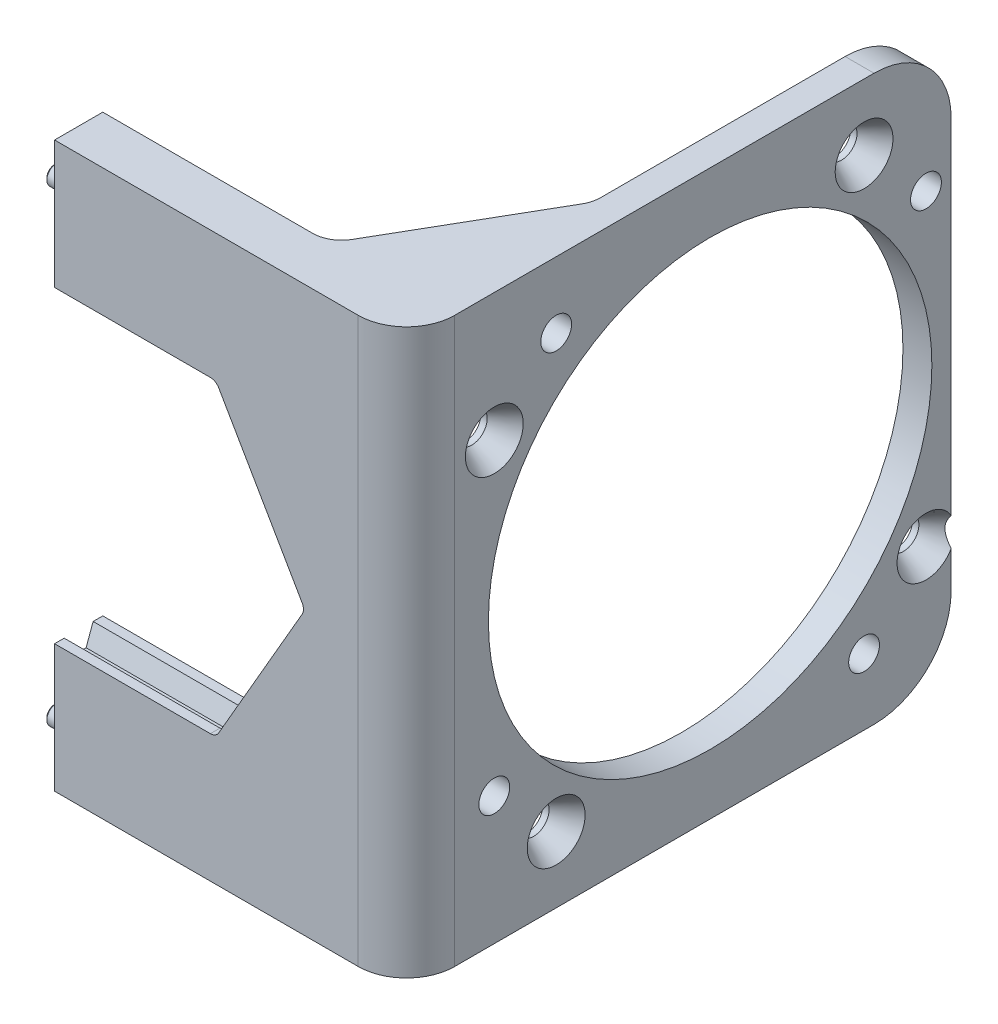
SolidWorks part; units mm, degrees
material "6061 合金"
ref_plane "前视基准面" through (0, 0, 0) normal (0, 0, 1) x (1, 0, 0)
ref_plane "上视基准面" through (0, 0, 0) normal (0, 1, 0) x (1, 0, 0)
ref_plane "右视基准面" through (0, 0, 0) normal (1, 0, 0) x (0, 0, -1)
other "Configuration Table"
sketch "草图1" plane through (0, 0, 0) normal (0, 0, 1) x (1, 0, 0)
  line L0 (-10.7623, 0) -> (8.7048, 0) construction
  line L1 (0, 6.2516) -> (0, -8.3883) construction
  circle A0 centre (0, 0) radius 18
  dimension "D1" = 36
extrude "凸台-拉伸1" add sketch "草图1" along normal blind 5
sketch "草图8" plane through (0, 0, 0) normal (0, 0, 1) x (1, 0, 0)
  line L0 (37.5243, 0) -> (-36.7763, 0) construction
  line L1 (0, 34.2207) -> (0, -32.974) construction
  line L2 (0, 26.25) -> (31, 26.25)
  line L3 (31, 26.25) -> (31, -26.25)
  line L4 (31, -26.25) -> (0, -26.25)
  line L5 (0, -26.25) -> (0, -18)
  line L6 (0, 26.25) -> (0, 18)
  circle A0 centre (0, 0) radius 18 construction
  arc A1 (0, -18) -> (0, 18) centre (0, 0) ccw
  dimension "D1" = 52.5
  dimension "D2" = 31
extrude "凸台-拉伸2" add sketch "草图8" along normal up to surface (5 mm away) up to face at (18, 0, 5)
sketch "草图9" plane through (0, 0, 0) normal (0, 0, -1) x (-1, 0, 0)
  line L0 (-31, 26.25) -> (0, 26.25) construction
  line L1 (-31, -26.25) -> (-26, -26.25)
  line L2 (-31, -26.25) -> (-31, 26.25)
  line L3 (-31, 26.25) -> (-26, 26.25)
  line L4 (-26, -26.25) -> (-26, 26.25)
  dimension "D1" = 5
extrude "凸台-拉伸3" add sketch "草图9" along normal blind 51.5
sketch "草图12" plane through (31, 0, 0) normal (1, 0, 0) x (0, 0, -1)
  line L1 (26.5, 0) -> (48.8882, 15.9693) construction
  line L2 (42.4693, 22.3882) -> (26.5, 0) construction
  line L3 (-6.3808, 0) -> (26.5, 0) construction
  line L4 (26.5, 0) -> (4.1118, 15.9693) construction
  line L5 (-5, -26.25) -> (-5, 26.25) construction
  circle A0 centre (26.5, 0) radius 27.5 construction
  circle A1 centre (4.1118, 15.9693) radius 1.6
  circle A2 centre (42.4693, 22.3882) radius 1.6
  circle A3 centre (48.8882, -15.9693) radius 1.6
  circle A4 centre (10.5307, -22.3882) radius 1.6
  circle A5 centre (48.8882, 15.9693) radius 1.6
  circle A6 centre (42.4693, -22.3882) radius 1.6
  circle A7 centre (4.1118, -15.9693) radius 1.6
  circle A8 centre (10.5307, 22.3882) radius 1.6
  point P22 (26.5, 0)
  point P27 (26.5, 0)
  dimension "D2" = 55
  dimension "D4" = 3.2
  dimension "D1" = 31.5
  dimension "D3" = 35.5
  dimension "D6" = 19
  dimension "D5" = 4
  dimension "D7" = 4
extrude "切除-拉伸1" cut sketch "草图12" against normal blind 45
sketch "草图25" plane through (0, 0, 0) normal (0, 0, -1) x (-1, 0, 0)
  line L0 (0, 16) -> (0, 26.25)
  line L1 (18.4752, 0) -> (9.2376, 16)
  line L2 (9.2376, 16) -> (-9.2376, 16)
  line L3 (-9.2376, 16) -> (-18.4752, 0)
  line L4 (-18.4752, 0) -> (-9.2376, -16)
  line L5 (-9.2376, -16) -> (9.2376, -16)
  line L6 (9.2376, -16) -> (18.4752, 0)
  line L7 (0, 26.25) -> (23.9717, 26.25)
  line L8 (23.9717, 26.25) -> (23.9717, -26.25)
  line L9 (23.9717, -26.25) -> (0, -26.25)
  line L10 (0, -26.25) -> (0, -16)
  circle A0 centre (0, 0) radius 16 construction
  line M6 (0, -26.25) -> (0, -18)
  arc M7 (0, -18) -> (0, 18) centre (0, 0) ccw
  line M8 (0, 18) -> (0, 26.25)
  dimension "D1" = 32
extrude "切除-拉伸7" cut sketch "草图25" against normal blind 10 contours L9 L8 L7 L2 L1 L6 L5 M8 M7 M6 | L1 M7 | L2 L0 M7 | L6 M7 | L10 L5 M7 region at (-3.1166, 16.8039, 0) region at (-0.5771, 22.125, 0) region at (-14.5526, 8.402, 0) region at (-3.1166, -16.8039, 0) region at (-14.5526, -8.402, 0)
extrude "切除-拉伸8" cut sketch "草图25<3>" against normal blind 10 contours L6 L1 L2 L3 L4 L5 M7 | L1 | L5 | L3 region at (0.0165, 0, 0) region at (-9.077, 15.7217, 0) region at (-9.077, -15.7217, 0)
sketch "草图25<3>" plane through (0, 0, 0) normal (0, 0, -1) x (-1, 0, 0) same geometry as "草图25"
sketch "草图26" plane through (0, 0, 0) normal (0, 0, -1) x (-1, 0, 0)
  line L0 (0, 26.25) -> (7.5, 26.25)
  line L1 (7.5, 26.25) -> (7.5, 16)
  line L2 (7.5, 16) -> (0, 16)
  line L3 (0, 16) -> (0, 26.25)
  line L4 (0, -16) -> (7.5, -16)
  line L5 (0, -16) -> (0, -26.25) construction
  line L6 (0, -16) -> (0, -26.25)
  line L7 (0, -26.25) -> (7.5, -26.25)
  line L8 (7.5, -26.25) -> (7.5, -16)
  dimension "D1" = 7.5
extrude "凸台-拉伸5" add sketch "草图26" against normal up to surface (5 mm away) up to face at (10.9945, 0, 5)
sketch "草图27" plane through (-7.5, 0, 0) normal (-1, 0, 0) x (0, 0, 1)
  line L0 (2.5, 16) -> (2.5, 50016) construction
  line L1 (5, 16) -> (0, 16) construction
  line L2 (1, 16) -> (1.7279, 18)
  line L3 (5, 16) -> (0, 16) construction
  line L4 (1.7279, 18) -> (2.5, 18)
  line L5 (3.2721, 18) -> (2.5, 18)
  line L6 (4, 16) -> (3.2721, 18)
  line L7 (1, 16) -> (4, 16)
  point P4 (2.5, 16)
  dimension "D1" = 3
  dimension "D2" = 40
  dimension "D3" = 2
ref_plane "基准面1" through (0, 0, 2.5) normal (0, 0, 1) x (1, 0, 0)
sketch "草图28" plane through (0, 0, 2.5) normal (0, 0, 1) x (1, 0, 0)
  line L0 (-7.5, -199984) -> (-7.5, 250016) construction
  line L1 (18.4752, 0) -> (9.2376, 16)
  line L2 (9.2376, 16) -> (-9.2376, 16)
  line L3 (-9.2376, 16) -> (-18.4752, 0)
  line L4 (-18.4752, 0) -> (-9.2376, -16)
  line L5 (-9.2376, -16) -> (9.2376, -16)
  line L6 (9.2376, -16) -> (18.4752, 0)
  circle A0 centre (0, 0) radius 16 construction
  dimension "D1" = 32
sweep "切除-扫描1" cut profiles "草图27" path "草图28"
fillet "圆角11" radius 1 6 edges at (9.2376, 16, 4.5) (9.2376, 16, 0.5) (9.2376, -16, 4.5) (9.2376, -16, 0.5) (18.4752, 0, 4.5) (18.4752, 0, 0.5)
sketch "草图14" plane through (31, 0, 0) normal (1, 0, 0) x (0, 0, -1)
  circle A0 centre (26.5, 0) radius 23
  dimension "D1" = 46
extrude "切除-拉伸2" cut sketch "草图14" against normal through all
sketch "草图21" plane through (0, 26.25, 0) normal (0, 1, 0) x (1, 0, 0)
  line L2 (26, 51.5) -> (26, 0) construction
  line L5 (-7.5, 0) -> (16, 0)
  line L6 (-7.5, -5) -> (31, -5)
  line L7 (31, -5) -> (31, 51.5)
  line L8 (31, 51.5) -> (26, 51.5)
  line L9 (26, 51.5) -> (26, 0)
  line L10 (26, 0) -> (-7.5, 0)
  line L12 (-7.5, -5) -> (31, -5)
  line L13 (31, -5) -> (31, 51.5)
  line L14 (31, 51.5) -> (26, 51.5)
  line L18 (26, 0) -> (-7.5, 0) construction
  line L19 (16, 0) -> (26, 17.3205)
  line L20 (26, 17.3205) -> (26, 51.5)
  line L29 (-7.5, 0) -> (-7.5, -5)
  line L30 (-7.5, 0) -> (-7.5, -5)
  dimension "D2" = 60
  dimension "D3" = 10
  dimension "D1" = 0
extrude "凸台-拉伸4" add sketch "草图21" along normal blind 3
mirror "镜向1" about plane through (0, 0, 0) normal (0, 1, 0) of "凸台-拉伸4"
sketch "草图36" plane through (31, 0, 0) normal (1, 0, 0) x (0, 0, -1)
  line L4 (-5, 29.25) -> (-5, -29.25)
  line L5 (-5, -29.25) -> (51.5, -29.25)
  line L6 (51.5, -29.25) -> (51.5, 29.25)
  line L7 (51.5, 29.25) -> (-5, 29.25)
  line L8 (-5, 29.25) -> (-5, -29.25)
  line L9 (-5, -29.25) -> (51.5, -29.25)
  line L10 (51.5, -29.25) -> (51.5, 29.25)
  line L11 (51.5, 29.25) -> (-5, 29.25)
  dimension "D1" = 0
extrude "切除-拉伸10" cut sketch "草图36" against normal blind 2
fillet "圆角4" radius 5 1 edges at (29, 0, 5)
fillet "圆角6" radius 8 2 edges at (27.5, -29.25, -51.5) (27.5, 29.25, -51.5)
fillet "圆角9" radius 3 4 edges at (16, 27.75, 0) (16, -27.75, 0) (26, -27.75, -17.3205) (26, 27.75, -17.3205)
fillet "圆角10" radius 2 5 edges at (20.134, -26.25, 0) (26, -26.25, -9.0622) (26, 0, 0) (26, 26.25, -9.0622) (20.134, 26.25, 0)
ref_axis "基准轴2" through (26, -22.3882, -10.5307) along (1, 0, 0)
ref_plane "基准面3" through (0, -22.3882, 0) normal (0, 1, 0) x (1, 0, 0)
sketch "草图40" plane through (0, -22.3882, 0) normal (0, 1, 0) x (1, 0, 0)
  line L0 (29, 10.5307) -> (26.0943, 10.5307) construction
  line L1 (26, 10.5307) -> (29, 10.5307) construction
  line L2 (29, 43.5) -> (29, 0) construction
  line L3 (29, 10.5307) -> (29, 13.5307)
  line L4 (29, 13.5307) -> (26.5, 12.0307)
  line L5 (26.5, 12.0307) -> (26.5, 10.5307)
  line L6 (26.5, 10.5307) -> (29, 10.5307)
  dimension "D1" = 6
  dimension "D2" = 3
  dimension "D3" = 2.5
revolve "切除-旋转2" cut sketch "草图40" angle 360 about L0
pattern_circular "阵列(圆周)2" count 4 every 90 about axis through (-7.5, 0, -26.5) along (1, 0, 0) of "切除-旋转2"
sketch "草图42" plane through (-7.5, 0, 0) normal (-1, 0, 0) x (0, 0, 1)
  line L0 (0, 0) -> (28.0878, 0) construction
  line L1 (0, 24.25) -> (0, -24.25) construction
  line L3 (0, 16) -> (0, 29.25) construction
  point P0 (2.5, -20.8)
  point P2 (2.5, 20.8)
  dimension "D1" = 20.8
  dimension "D2" = 2.5
  dimension "D3" = 20.8
hole_wizard "M3 螺纹孔1" positions "草图42" profile "草图43" tap size "M3" standard "GB"
sketch "草图43" plane through (-7.5, -20.8, 2.5) normal (0, 1, 0) x (0, 0, 1)
  line L0 (0, 0) -> (0, 6.2511)
  line L1 (0, 6.2511) -> (1.25, 5.5)
  line L2 (1.25, 5.5) -> (1.25, 0)
  line L5 (1.25, 0) -> (0, 0)
  line L10 (0, 6.2511) -> (-1.25, 5.5) construction
  line L11 (0, -6.35) -> (0, 107.95) construction
  dimension "螺纹孔钻头直径" = 2.5
  dimension "螺纹孔钻头深度" = 5.5
  dimension "导头角度" = 118
cosmetic thread "孔螺蚊线3" parameters "D1"=4, "D2"=3
cosmetic thread "孔螺蚊线4" parameters "D1"=4, "D2"=3
sketch "草图44" plane through (-7.5, 0, 0) normal (-1, 0, 0) x (0, 0, 1)
  line L0 (0, 0) -> (20.1775, 0) construction
  line L1 (0, 24.25) -> (0, -24.25) construction
  line L2 (2, -24.25) -> (3, -24.25) construction
  line L3 (2, -23.25) -> (3, -23.25)
  line L4 (2, -25.25) -> (3, -25.25)
  line L5 (0, -29.25) -> (0, -16) construction
  line L6 (5, -29.25) -> (5, -16) construction
  line L7 (0, -29.25) -> (5, -29.25) construction
  line L8 (2, 24.25) -> (3, 24.25) construction
  line L9 (2, 23.25) -> (3, 23.25)
  line L10 (2, 25.25) -> (3, 25.25)
  arc A0 (2, -23.25) -> (2, -25.25) centre (2, -24.25) ccw
  arc A1 (3, -25.25) -> (3, -23.25) centre (3, -24.25) ccw
  arc A2 (2, 23.25) -> (2, 25.25) centre (2, 24.25) cw
  arc A3 (3, 25.25) -> (3, 23.25) centre (3, 24.25) cw
  point P6 (2.5, -24.25)
  point P19 (2.5, 24.25)
  dimension "D3" = 1
  dimension "D1" = 2
  dimension "D2" = 2
  dimension "D4" = 5
extrude "凸台-拉伸6" add sketch "草图44" along normal blind 2
chamfer "倒角1" distance 0.2 angle 45 8 edges at (-9.5, 25.25, 2.5) (-9.5, 24.25, 1) (-9.5, 24.25, 4) (-9.5, 23.25, 2.5) (-9.5, -23.25, 2.5) (-9.5, -24.25, 1) (-9.5, -24.25, 4) (-9.5, -25.25, 2.5)
fillet "圆角12" radius 3 6 edges at (10.3923, 18, 2.886) (20.7846, 0, 2.886) (10.3923, -18, 2.886) (10.3923, 18, 2.114) (20.7846, 0, 2.114) (10.3923, -18, 2.114)
